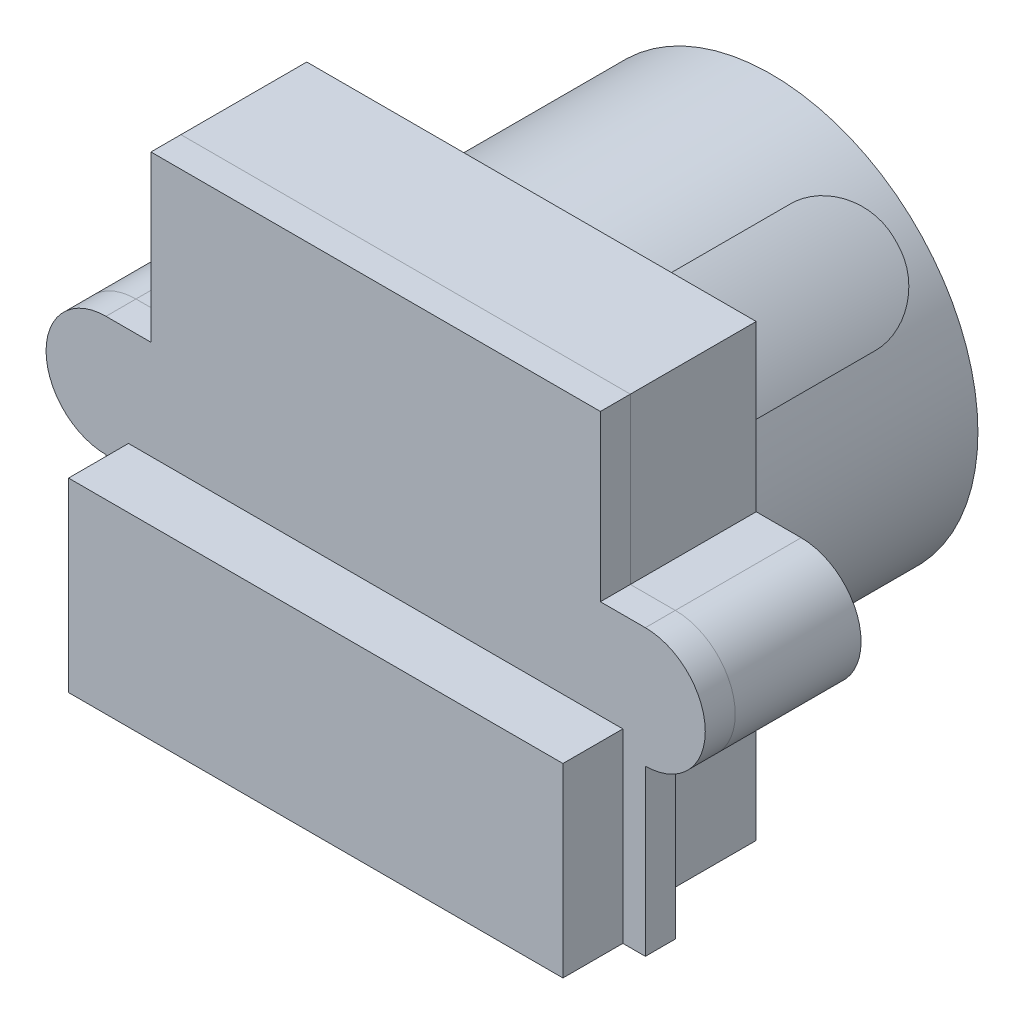
SolidWorks part; units mm, degrees
ref_plane "Front Plane" through (0, 0, 0) normal (0, 0, 1) x (1, 0, 0)
ref_plane "Top Plane" through (0, 0, 0) normal (0, 1, 0) x (1, 0, 0)
ref_plane "Right Plane" through (0, 0, 0) normal (1, 0, 0) x (0, 0, -1)
sketch "Sketch1" plane through (0, 0, 0) normal (0, 0, 1) x (1, 0, 0)
  line L0 (0, 0) -> (5.6569, 5.6569) construction
  line L1 (55, 0) -> (-55, 0) construction
  line L2 (3.2554, 6.0838) -> (4.063, 6.8914)
  line L3 (6.8914, 4.063) -> (6.0838, 3.2554)
  circle A0 centre (0, 0) radius 6.9
  arc A1 (6.8914, 4.063) -> (4.063, 6.8914) centre (0, 0) ccw
  circle A3 centre (0, 0) radius 8 construction
  point P12 (9.4234, 0)
  dimension "D1" = 13.8
  dimension "D4" = 4
  dimension "D2" = 45
  dimension "D3" = 1.1
extrude "Boss-Extrude1" add sketch "Sketch1" against normal blind 8 contours A0 region at (0, 0, 0)
extrude "Boss-Extrude2" add sketch "Sketch1<3>" against normal blind 6.5 contours L3 A1 L2 A0 region at (5.2029, 5.2029, 0)
sketch "Sketch1<3>" plane through (0, 0, 0) normal (0, 0, 1) x (1, 0, 0) same geometry as "Sketch1"
fillet "Fillet1" radius 1.905 2 edges at (3.6592, 6.4876, -6.5) (6.4876, 3.6592, -6.5) tangent propagation no
hole_wizard "Tap Drill for M12 Tap1" positions "Sketch3" profile "Sketch2" hole size "M12" standard "ISO" end condition through all
sketch "Sketch3" plane through (0, 0, -8) normal (0, 0, -1) x (-1, 0, 0)
  point P0 (0, 0)
sketch "Sketch2" plane through (0, 0, -8) normal (1, 0, 0) x (0, 1, 0)
  line L0 (0, 0) -> (0, 8)
  line L1 (0, 8) -> (5.1, 8)
  line L2 (5.1, 8) -> (5.1, 0)
  line L5 (5.1, 0) -> (0, 0)
  line L11 (0, -6.35) -> (0, 107.95) construction
  dimension "Thru Hole Dia." = 10.2
  dimension "Thru Hole Depth" = 8
sketch "Sketch4" plane through (0, 0, 0) normal (0, 0, 1) x (1, 0, 0)
  line L0 (0, 7.5) -> (0, -7.5) construction
  line L1 (-7.5, 7.5) -> (7.5, 7.5)
  line L2 (-7.5, 7.5) -> (-7.5, 2)
  line L3 (-7.5, -7.5) -> (7.5, -7.5)
  line L4 (7.5, 7.5) -> (7.5, 2)
  line L5 (7.5, 2) -> (9, 2)
  line L6 (-7.5, 0) -> (7.5, 0) construction
  line L7 (7.5, -2) -> (9, -2)
  line L8 (7.5, 0) -> (11, 0) construction
  line L9 (7.5, -2) -> (7.5, -7.5)
  line L10 (-7.5, 0) -> (-11, 0) construction
  line L11 (-7.5, -2) -> (-9, -2)
  line L12 (-7.5, 2) -> (-9, 2)
  line L13 (-7.5, -2) -> (-7.5, -7.5)
  arc A0 (9, -2) -> (9, 2) centre (9, 0) ccw
  arc A1 (-9, -2) -> (-9, 2) centre (-9, 0) cw
  circle A2 centre (9, 0) radius 0.5
  circle A3 centre (-9, 0) radius 0.5
  dimension "D5" = 1
  dimension "D1" = 15
  dimension "D2" = 15
  dimension "D3" = 4
  dimension "D4" = 3.5
extrude "Boss-Extrude3" add sketch "Sketch4" along normal blind 4.2
sketch "Sketch5" plane through (0, 0, 4.2) normal (0, 0, 1) x (1, 0, 0)
  line L0 (9, -2) -> (9, -7.5)
  line L1 (-9, -7.5) -> (9, -7.5)
  line L2 (-9, -7.5) -> (-9, -2)
  line L3 (-7.5, -7.5) -> (7.5, -7.5) construction
  line L10 (-7.5, 7.5) -> (-7.5, 2)
  line L11 (-7.5, 2) -> (-9, 2)
  line L12 (-9, -2) -> (-7.5, -2)
  line L13 (-7.5, -2) -> (-7.5, -7.5)
  line L14 (-7.5, -7.5) -> (7.5, -7.5)
  line L15 (7.5, -7.5) -> (7.5, -2)
  line L16 (7.5, -2) -> (9, -2)
  line L17 (9, 2) -> (7.5, 2)
  line L18 (7.5, 2) -> (7.5, 7.5)
  line L19 (7.5, 7.5) -> (-7.5, 7.5)
  line L20 (-7.5, 7.5) -> (-7.5, 2)
  line L21 (-7.5, 2) -> (-9, 2)
  line L27 (9, 2) -> (7.5, 2)
  line L28 (7.5, 2) -> (7.5, 7.5)
  line L29 (7.5, 7.5) -> (-7.5, 7.5)
  arc A2 (-9, 2) -> (-9, -2) centre (-9, 0) ccw
  arc A3 (9, -2) -> (9, 2) centre (9, 0) ccw
  arc A4 (-9, 2) -> (-9, -2) centre (-9, 0) ccw
  arc A5 (9, -2) -> (9, 2) centre (9, 0) ccw
  dimension "D1" = 0
extrude "Boss-Extrude4" add sketch "Sketch5" along normal blind 1 separate body
sketch "Sketch6" plane through (0, 0, 5.2) normal (0, 0, 1) x (1, 0, 0)
  line L0 (0, -1.3) -> (0, -7.5) construction
  line L1 (-8.25, -1.3) -> (8.25, -1.3)
  line L2 (-8.25, -1.3) -> (-8.25, -7.5)
  line L3 (-8.25, -7.5) -> (8.25, -7.5)
  line L4 (8.25, -1.3) -> (8.25, -7.5)
  line L5 (-9, -7.5) -> (9, -7.5) construction
  dimension "D1" = 16.5
  dimension "D2" = 6.2
extrude "Boss-Extrude5" add sketch "Sketch6" along normal blind 2 separate body
sketch "Sketch8" plane through (0, 0, 0) normal (1, 0, 0) x (0, 0, -1)
  line L1 (6.5, 0) -> (0, 0) construction
  line L2 (-6.2, 0) -> (-6.2, -7.5) construction
  line L3 (-4.2, 7.5) -> (-4.2, 2) construction
  line L4 (-4.2, -7.5) -> (0, -7.5) construction
  dimension "D1" = 2
ref_plane "Plane1" through (0, 0, 6.2) normal (0, 0, 1) x (1, 0, 0)
sketch "Sketch9" plane through (0, 0, 6.2) normal (0, 0, 1) x (1, 0, 0)
  line L0 (-12.7, -7.5) -> (12.7, -7.5) construction
  dimension "D1" = 12.7
